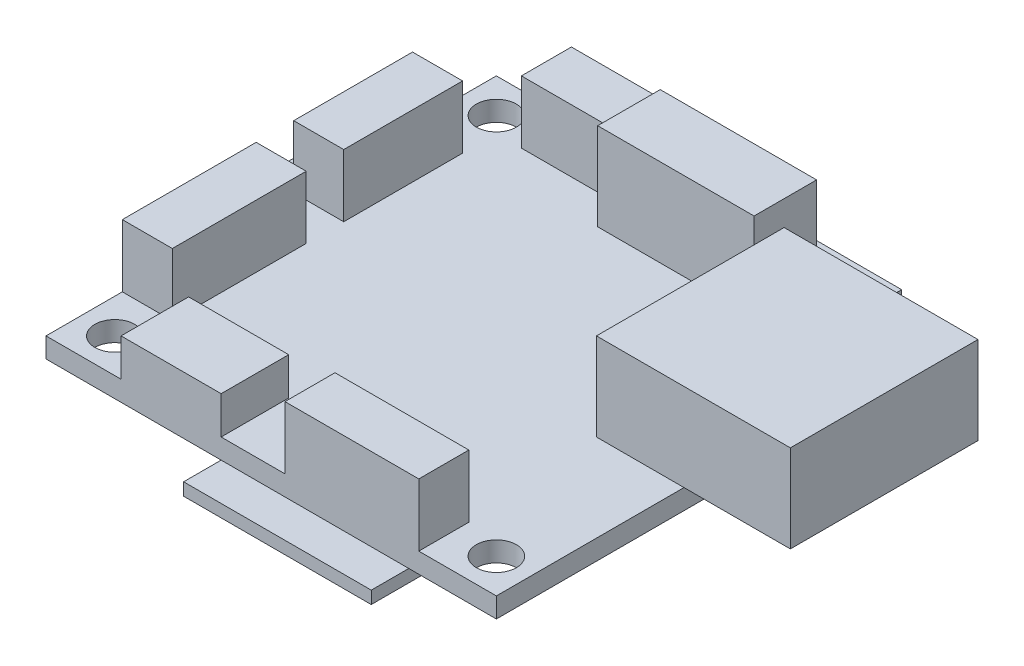
SolidWorks part; units mm, degrees
ref_plane "Ebene vorne" through (0, 0, 0) normal (0, 0, 1) x (1, 0, 0)
ref_plane "Ebene oben" through (0, 0, 0) normal (0, 1, 0) x (1, 0, 0)
ref_plane "Ebene rechts" through (0, 0, 0) normal (1, 0, 0) x (0, 0, -1)
sketch "Sketch1" plane through (0, 0, 0) normal (0, 1, 0) x (1, 0, 0)
  line L0 (0, 14.5059) -> (0, -19.8) construction
  line L1 (-13.9765, 0) -> (32.6118, 0) construction
  line L3 (-18, 18) -> (18, 18)
  line L4 (-18, 18) -> (-18, -18)
  line L5 (-18, -18) -> (18, -18)
  line L6 (18, 18) -> (18, -18)
  circle A0 centre (-15.25, 15.25) radius 1.6
  circle A1 centre (15.25, 15.25) radius 1.6
  circle A2 centre (15.25, -15.25) radius 1.6
  circle A3 centre (-15.25, -15.25) radius 1.6
  dimension "D3" = 3.2
  dimension "D1" = 36
  dimension "D2" = 36
  dimension "D4" = 30.5
  dimension "D5" = 30.5
extrude "Boss-Extrude1" add sketch "Sketch1" along normal blind 1.6
sketch "Sketch2" plane through (18, 0, 0) normal (1, 0, 0) x (0, 0, -1)
  line L0 (18, 1.6) -> (18, 0) construction
  line L1 (-3, 8.6) -> (12, 8.6)
  line L2 (-3, 8.6) -> (-3, 1.6)
  line L3 (-3, 1.6) -> (12, 1.6)
  line L4 (12, 8.6) -> (12, 1.6)
  line L6 (-18, 1.6) -> (18, 1.6) construction
  dimension "D1" = 15
  dimension "D2" = 7
  dimension "D3" = 6
extrude "ServoConnector" add sketch "Sketch2" along normal blind 8.5 and the other way blind 7
sketch "Sketch3" plane through (0, 0, 18) normal (0, 0, 1) x (1, 0, 0)
  line L1 (-4, 0) -> (11, 0)
  line L2 (-4, 0) -> (-4, -1)
  line L3 (-4, -1) -> (11, -1)
  line L4 (11, 0) -> (11, -1)
  line L5 (18, 1.6) -> (18, 0) construction
  line L6 (-18, 0) -> (18, 0) construction
  dimension "D1" = 15
  dimension "D2" = 1
  dimension "D4" = 7
extrude "SDCard" add sketch "Sketch3" along normal blind 3 and the other way blind 15
sketch "Sketch4" plane through (0, 1.6, 0) normal (0, 1, 0) x (1, 0, 0)
  line L1 (-3.5, 16.6) -> (9, 16.6)
  line L2 (-3.5, 16.6) -> (-3.5, 11.6)
  line L3 (-3.5, 11.6) -> (9, 11.6)
  line L4 (9, 16.6) -> (9, 11.6)
  line L6 (18, 12) -> (18, 18) construction
  line L8 (18, 18) -> (-18, 18) construction
  dimension "D1" = 12.5
  dimension "D2" = 5
  dimension "D3" = 9
  dimension "D4" = 1.4
extrude "NC" add sketch "Sketch4" along normal blind 7
sketch "Sketch5" plane through (0, 1.6, 0) normal (0, 1, 0) x (1, 0, 0)
  line L0 (18, 18) -> (-18, 18) construction
  line L1 (-12, 18) -> (-4, 18)
  line L2 (-12, 18) -> (-12, 14)
  line L3 (-12, 14) -> (-4, 14)
  line L4 (-4, 18) -> (-4, 14)
  line L5 (-18, 18) -> (-18, -18) construction
  dimension "D1" = 4
  dimension "D2" = 8
  dimension "D3" = 6
extrude "NC2" add sketch "Sketch5" along normal blind 5
sketch "Sketch6" plane through (0, 1.6, 0) normal (0, 1, 0) x (1, 0, 0)
  line L0 (-18, 18) -> (-18, -18) construction
  line L1 (-18, 11.3) -> (-14, 11.3)
  line L2 (-18, 11.3) -> (-18, 1.8)
  line L3 (-18, 1.8) -> (-14, 1.8)
  line L4 (-14, 11.3) -> (-14, 1.8)
  line L5 (-12, 18) -> (-18, 18) construction
  line L6 (-18, -1.2) -> (-14, -1.2)
  line L7 (-18, -1.2) -> (-18, -11.9)
  line L8 (-18, -11.9) -> (-14, -11.9)
  line L9 (-14, -1.2) -> (-14, -11.9)
  point P12 (-15, 18)
  dimension "D1" = 9.5
  dimension "D2" = 4
  dimension "D3" = 4
  dimension "D4" = 10.7
  dimension "D5" = 3
  dimension "D6" = 6.7
extrude "NC3" add sketch "Sketch6" along normal blind 5
sketch "Sketch7" plane through (0, 1.6, 0) normal (0, 1, 0) x (1, 0, 0)
  line L0 (-18, -18) -> (18, -18) construction
  line L1 (-12, -12.6) -> (-4, -12.6)
  line L2 (-12, -12.6) -> (-12, -18)
  line L3 (-12, -18) -> (-4, -18)
  line L4 (-4, -12.6) -> (-4, -18)
  line L5 (-18, -11.9) -> (-18, -18) construction
  line L7 (1.1, -14) -> (11.8, -14)
  line L8 (1.1, -14) -> (1.1, -18)
  line L9 (1.1, -18) -> (11.8, -18)
  line L10 (11.8, -14) -> (11.8, -18)
  dimension "D1" = 8
  dimension "D2" = 5.4
  dimension "D3" = 6
  dimension "D4" = 10.7
  dimension "D5" = 4
  dimension "D6" = 5.1
extrude "MicroUsb" add sketch "Sketch7" along normal blind 3 contours L1 L4 L3 L2
extrude "NC4" add sketch "Sketch7<3>" along normal blind 5 contours L7 L10 L9 L8
sketch "Sketch7<3>" plane through (0, 1.6, 0) normal (0, 1, 0) x (1, 0, 0) same geometry as "Sketch7"
sketch "Sketch8" plane through (0, 0, 0) normal (0, -1, 0) x (-1, 0, 0)
  line L0 (18, 18) -> (18, -18) construction
  line L1 (18, 0.5) -> (14, 0.5)
  line L2 (18, 0.5) -> (18, 11.5)
  line L3 (18, 11.5) -> (14, 11.5)
  line L4 (14, 0.5) -> (14, 11.5)
  line L5 (-18, 18) -> (18, 18) construction
  dimension "D1" = 11
  dimension "D2" = 6.5
  dimension "D3" = 4
extrude "GPS and Pitot" add sketch "Sketch8" along normal blind 5
sketch "Sketch9" plane through (-18, 0, 0) normal (-1, 0, 0) x (0, 0, 1)
  line L0 (-11.5, -5) -> (-11.5, 0) construction
  line L1 (-11.2, 0) -> (-0.8, 0)
  line L2 (-11.2, 0) -> (-11.2, -4.7)
  line L3 (-11.2, -4.7) -> (-0.8, -4.7)
  line L4 (-0.8, 0) -> (-0.8, -4.7)
  line L5 (-0.5, -5) -> (-11.5, -5) construction
  line L6 (-0.5, -5) -> (-0.5, 0) construction
  line L7 (-0.5, 0) -> (18, 0) construction
  dimension "D1" = 0.3
  dimension "D2" = 0.3
  dimension "D3" = 0.3
extrude "ConnectorGPSPitot" add sketch "Sketch9" along normal blind 4
sketch "Sketch10" plane through (0, 0, 0) normal (0, -1, 0) x (1, 0, 0)
  line L0 (18, -18) -> (-18, -18) construction
  line L1 (-12.6, -14) -> (-2.6, -14)
  line L2 (-12.6, -14) -> (-12.6, -18)
  line L3 (-12.6, -18) -> (-2.6, -18)
  line L4 (-2.6, -14) -> (-2.6, -18)
  line L5 (18, 18) -> (18, -18) construction
  line L6 (0.7, -14) -> (11.7, -14)
  line L7 (0.7, -14) -> (0.7, -18)
  line L8 (0.7, -18) -> (11.7, -18)
  line L9 (11.7, -14) -> (11.7, -18)
  point P10 (11.7, -16)
  dimension "D1" = 11
  dimension "D2" = 6.3
  dimension "D3" = 10
  dimension "D4" = 3.3
  dimension "D5" = 4
  dimension "D6" = 4
extrude "NC5" add sketch "Sketch10" along normal blind 5 contours L1 L4 L3 L2
extrude "Power" add sketch "Sketch10<3>" along normal blind 5 contours L6 L9 L8 L7
sketch "Sketch10<3>" plane through (0, 0, 0) normal (0, -1, 0) x (1, 0, 0) same geometry as "Sketch10"
sketch "Sketch11" plane through (0, 0, -18) normal (0, 0, -1) x (-1, 0, 0)
  line L0 (-0.7, -5) -> (-11.7, -5) construction
  line L1 (-11.4, 0) -> (-1, 0)
  line L2 (-11.4, 0) -> (-11.4, -4.7)
  line L3 (-11.4, -4.7) -> (-1, -4.7)
  line L4 (-1, 0) -> (-1, -4.7)
  line L5 (-11.7, -5) -> (-11.7, 0) construction
  line L6 (-0.7, -5) -> (-0.7, 0) construction
  line L7 (-0.7, 0) -> (-11.7, 0) construction
  dimension "D1" = 0.3
  dimension "D2" = 0.3
  dimension "D3" = 0.3
extrude "Boss-Extrude13" add sketch "Sketch11" along normal blind 3
